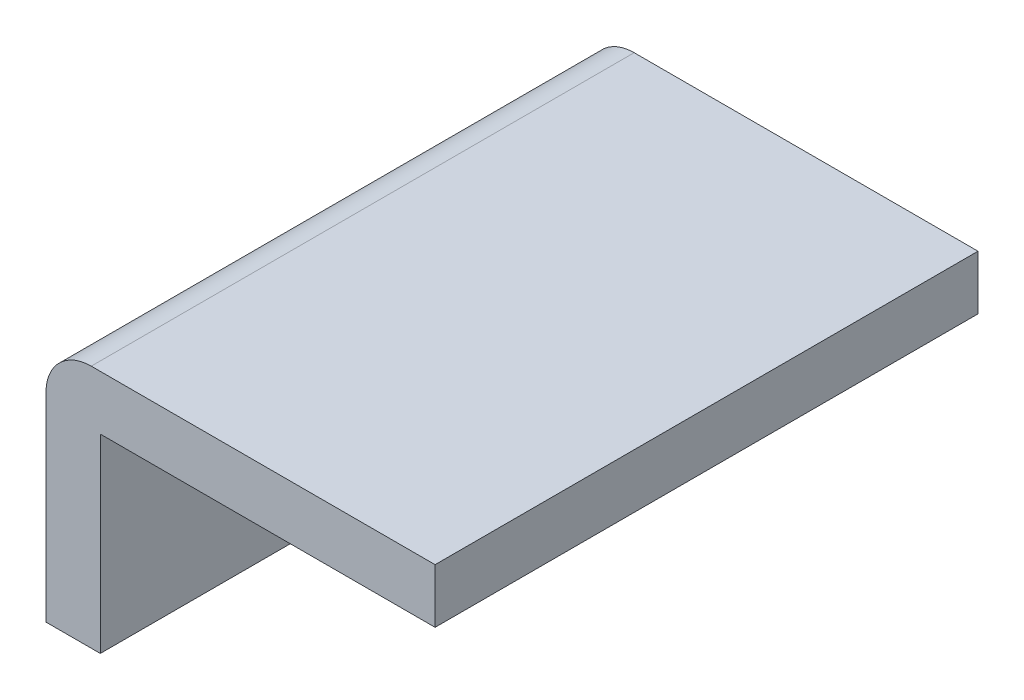
SolidWorks part; units mm, degrees
material "Acrilico TEC"
ref_plane "Front Plane" through (0, 0, 0) normal (0, 0, 1) x (1, 0, 0)
ref_plane "Top Plane" through (0, 0, 0) normal (0, 1, 0) x (1, 0, 0)
ref_plane "Right Plane" through (0, 0, 0) normal (1, 0, 0) x (0, 0, -1)
sketch "Sketch1" plane through (0, 0, 0) normal (0, 0, 1) x (1, 0, 0)
  line L0 (0, 0) -> (0, 11)
  line L1 (1, 12) -> (20, 12)
  line L2 (1.5, 0) -> (1.5, 10.5)
  line L3 (1.5, 10.5) -> (20, 10.5)
  line L4 (-1.5, 0) -> (-1.5, 11)
  line L5 (1, 13.5) -> (20, 13.5)
  line L6 (20, 13.5) -> (20, 10.5)
  line L7 (-1.5, 0) -> (1.5, 0)
  arc A0 (0, 11) -> (1, 12) centre (1, 11) cw
  arc A1 (1.5, 10.5) -> (1.5, 10.5) centre (1.5, 10.5) cw
  arc A2 (-1.5, 11) -> (1, 13.5) centre (1, 11) cw
  point P6 (0, 12)
  dimension "D3" = 1
  dimension "D1" = 20
  dimension "D2" = 12
  dimension "D4" = 1.5
  dimension "D5" = 1.5
extrude "Boss-Extrude1" add sketch "Sketch1" along normal blind 30 contours A0 L0 L7 L2 L3 L6 L1 | A2 L4 L7 L0 A0 L1 L6 L5 region at (-0.75, 0.2539, 0) region at (0.2332, 5.5, 0)
hole_wizard "Ø2.0mm Clearance Dowel Hole1" positions "Sketch2" profile "Sketch3" hole size "Ø2.0" standard "ISO" rebuild error yes end condition through all
sketch "Sketch2" plane through (-35.9294, 10.5, -58.5) normal (0, -1, 0) x (-1, 0, 0)
  point P0 (-26.9294, -76.5)
  point P1 (-26.9294, -70.5)
sketch "Sketch3" plane through (-9, 10.5, 18) normal (1, 0, 0) x (0, 0, -1)
  line L0 (0, 0) -> (0, 3)
  line L1 (0, 3) -> (1, 3)
  line L2 (1, 3) -> (1, 0)
  line L3 (1, 0) -> (0, 0)
  line L4 (0, -6.35) -> (0, 107.95) construction
  dimension "Thru Hole Dia." = 2
  dimension "Thru Hole Depth" = 3
